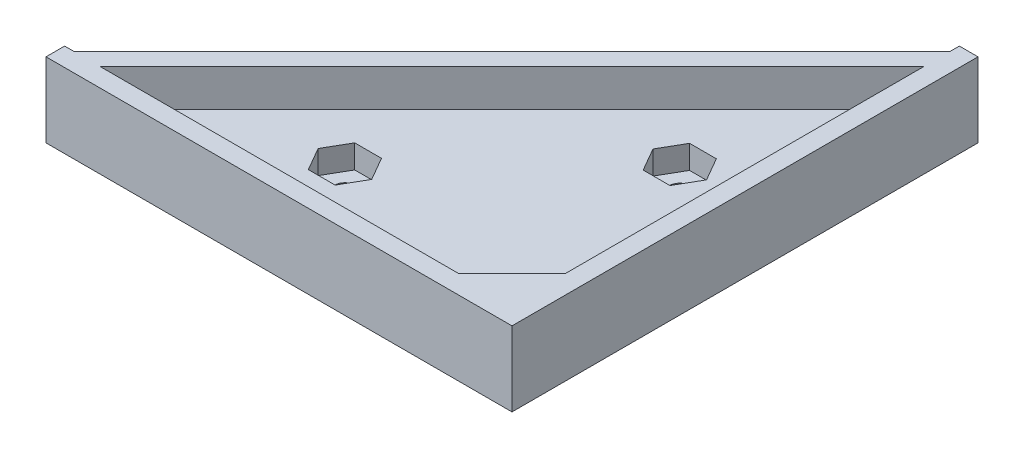
SolidWorks part; units mm, degrees
ref_plane "Front Plane" through (0, 0, 0) normal (0, 0, 1) x (1, 0, 0)
ref_plane "Top Plane" through (0, 0, 0) normal (0, 1, 0) x (1, 0, 0)
ref_plane "Right Plane" through (0, 0, 0) normal (1, 0, 0) x (0, 0, -1)
sketch "Sketch1" plane through (0, 0, 0) normal (0, 1, 0) x (1, 0, 0)
  line L0 (-79.375, 0) -> (0, 0)
  line L1 (0, 0) -> (0, 79.375)
  line L2 (0, 79.375) -> (-3.175, 79.375)
  line L3 (-3.175, 79.375) -> (-3.175, 77.7875)
  line L4 (-3.175, 77.7875) -> (-77.7875, 3.175)
  line L5 (-77.7875, 3.175) -> (-79.375, 3.175)
  line L6 (-79.375, 3.175) -> (-79.375, 0)
  dimension "D1" = 76.2
  dimension "D2" = 79.375
  dimension "D3" = 3.175
  dimension "D4" = 1.5875
extrude "Boss-Extrude1" add sketch "Sketch1" along normal blind 12.7
sketch "Sketch2" plane through (0, 12.7, 0) normal (0, 1, 0) x (1, 0, 0)
  line L0 (-73.2974, 3.175) -> (-12.2411, 3.175)
  line L1 (-3.175, 12.2411) -> (-3.175, 73.2974)
  line L2 (-3.175, 73.2974) -> (-73.2974, 3.175)
  line L3 (-12.2411, 3.175) -> (-3.175, 12.2411)
  line L5 (-79.375, 0) -> (0, 0) construction
  line L6 (0, 0) -> (0, 79.375) construction
  line L7 (-3.175, 77.7875) -> (-77.7875, 3.175) construction
  dimension "D2" = 3.175
  dimension "D3" = 3.175
  dimension "D4" = 3.175
extrude "Cut-Extrude1" cut sketch "Sketch2" against normal blind 6.35
chamfer "Chamfer1" distance 6.35 angle 45 1 edges at (-7.708, 6.35, -7.708)
sketch "Sketch3" plane through (0, 6.35, 0) normal (0, 1, 0) x (1, 0, 0)
  line L0 (-79.375, 0) -> (0, 0) construction
  line L1 (0, 0) -> (0, 79.375) construction
  circle A0 centre (-44.4608, 16.002) radius 1.75
  circle A1 centre (-15.875, 44.45) radius 1.75
  dimension "D1" = 3.5
  dimension "D2" = 3.5
  dimension "D3" = 16.002
  dimension "D4" = 44.4608
  dimension "D5" = 15.875
  dimension "D6" = 44.45
extrude "Cut-Extrude2" cut sketch "Sketch3" against normal blind 6.35
sketch "Sketch4" plane through (0, 6.35, 0) normal (0, 1, 0) x (1, 0, 0)
  line L1 (-13.5945, 40.5) -> (-11.3139, 44.45)
  line L2 (-11.3139, 44.45) -> (-13.5945, 48.4)
  line L3 (-13.5945, 48.4) -> (-18.1555, 48.4)
  line L4 (-18.1555, 48.4) -> (-20.4361, 44.45)
  line L5 (-20.4361, 44.45) -> (-18.1555, 40.5)
  line L6 (-18.1555, 40.5) -> (-13.5945, 40.5)
  line L7 (-39.8997, 16.002) -> (-42.1803, 19.952)
  line L8 (-42.1803, 19.952) -> (-46.7413, 19.952)
  line L9 (-46.7413, 19.952) -> (-49.0219, 16.002)
  line L10 (-49.0219, 16.002) -> (-46.7413, 12.052)
  line L11 (-46.7413, 12.052) -> (-42.1803, 12.052)
  line L12 (-42.1803, 12.052) -> (-39.8997, 16.002)
  circle A0 centre (-44.4608, 16.002) radius 1.75 construction
  circle A1 centre (-15.875, 44.45) radius 1.75 construction
  circle A2 centre (-44.4608, 16.002) radius 1.75
  circle A3 centre (-15.875, 44.45) radius 1.75
  circle A4 centre (-15.875, 44.45) radius 3.95 construction
  circle A5 centre (-44.4608, 16.002) radius 3.95 construction
  dimension "D1" = 7.9
  dimension "D2" = 7.9
extrude "Cut-Extrude3" cut sketch "Sketch4" against normal blind 4
